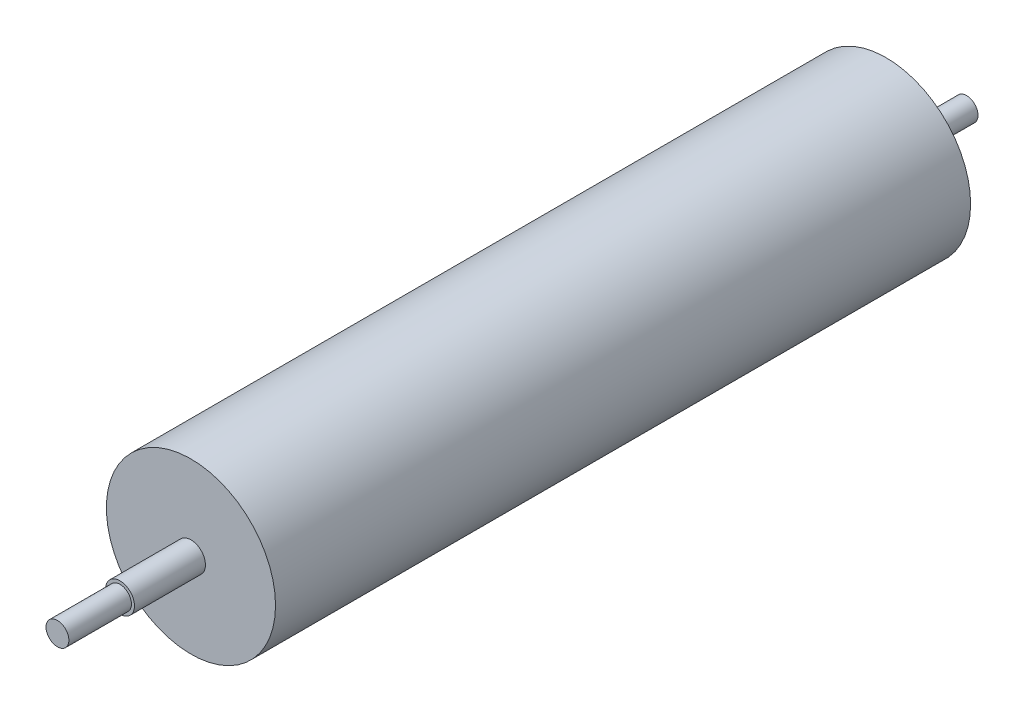
SolidWorks part; units mm, degrees
material "1060 Alloy"
ref_plane "Front Plane" through (0, 0, 0) normal (0, 0, 1) x (1, 0, 0)
ref_plane "Top Plane" through (0, 0, 0) normal (0, 1, 0) x (1, 0, 0)
ref_plane "Right Plane" through (0, 0, 0) normal (1, 0, 0) x (0, 0, -1)
sketch "Sketch1" plane through (0, 0, 0) normal (0, 0, 1) x (1, 0, 0)
  circle A0 centre (0, 0) radius 5
  circle A1 centre (0, 0) radius 3.95
  circle A2 centre (0, 0) radius 29.2
  dimension "D1" = 10
  dimension "D2" = 7.9
extrude "Boss-Extrude1" add sketch "Sketch1" along normal blind 240 contours A2 A0 | A0 A1 | A1 region at (-4.8586, 0, 0) region at (0, 0, 0) region at (-28.3741, 0, 0)
extrude "Boss-Extrude2" add sketch "Sketch1<3>" against normal blind 15.5 contours A0
sketch "Sketch1<3>" plane through (0, 0, 0) normal (0, 0, 1) x (1, 0, 0) same geometry as "Sketch1"
extrude "Boss-Extrude3" add sketch "Sketch1<4>" against normal blind 12.3 from surface contours A1 region at (0, 0, 0) starting at face at (5, 0, -15.5)
sketch "Sketch1<4>" plane through (0, 0, 0) normal (0, 0, 1) x (1, 0, 0) same geometry as "Sketch1"
extrude "Boss-Extrude4" add sketch "Sketch1<5>" along normal blind 24.5 from surface contours A1 | A0 A1 region at (-4.8586, 0, 0) region at (0, 0, 0) starting at face at (29.2, 0, 240)
sketch "Sketch1<5>" plane through (0, 0, 0) normal (0, 0, 1) x (1, 0, 0) same geometry as "Sketch1"
extrude "Boss-Extrude5" add sketch "Sketch1<6>" along normal blind 21.6 from surface contours A1 region at (0, 0, 0) starting at face at (5, 0, 264.5)
sketch "Sketch1<6>" plane through (0, 0, 0) normal (0, 0, 1) x (1, 0, 0) same geometry as "Sketch1"
